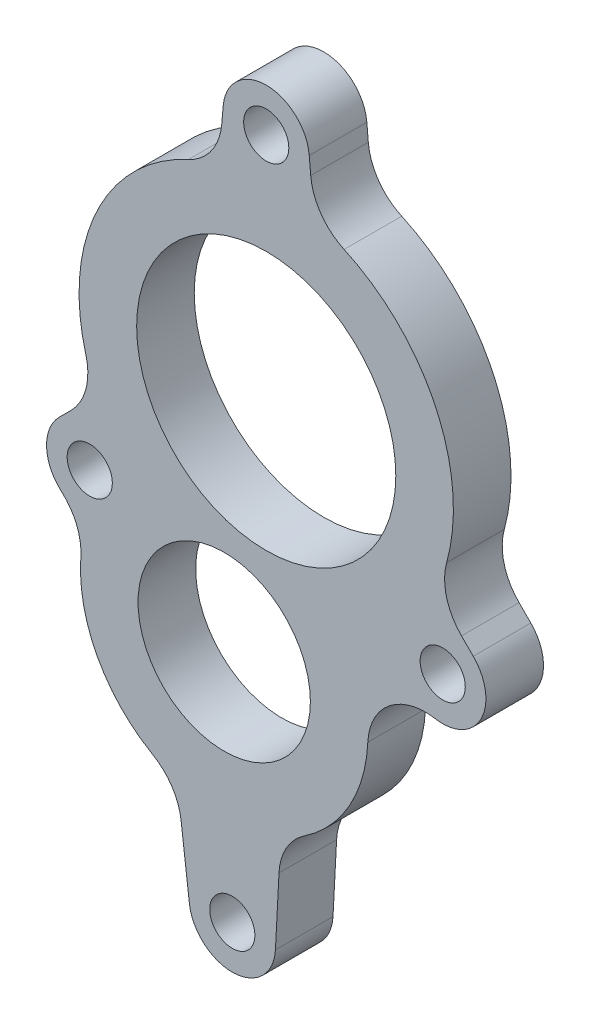
SolidWorks part; units mm, degrees
material "6061-T6 (SS)"
ref_plane "Front Plane" through (0, 0, 0) normal (0, 0, 1) x (1, 0, 0)
ref_plane "Top Plane" through (0, 0, 0) normal (0, 1, 0) x (1, 0, 0)
ref_plane "Right Plane" through (0, 0, 0) normal (1, 0, 0) x (0, 0, -1)
sketch "Sketch1" plane through (0, 0, 0) normal (0, 0, 1) x (1, 0, 0)
  line L0 (0, 0) -> (0, 25.4) construction
  line L1 (0, 0) -> (19.4575, -16.3268) construction
  line L2 (0, 0) -> (-19.4575, -16.3268) construction
  line L3 (-4.7444, 25.8151) -> (-5.2569, 19.9567)
  line L4 (4.7444, 25.8151) -> (5.2569, 19.9567)
  line L5 (22.8251, -12.9592) -> (18.6668, -8.8009)
  line L6 (16.7259, -20.228) -> (11.9087, -16.855)
  line L7 (-16.7259, -20.228) -> (-11.9087, -16.855)
  line L8 (-18.6668, -8.8009) -> (-22.8251, -12.9592)
  circle A0 centre (19.4575, -16.3268) radius 4.7625
  circle A1 centre (0, 25.4) radius 4.7625
  circle A2 centre (-19.4575, -16.3268) radius 4.7625
  circle A3 centre (19.4575, -16.3268) radius 2.4892
  circle A4 centre (-19.4575, -16.3268) radius 2.4892
  circle A5 centre (0, 25.4) radius 2.4892
  circle A6 centre (0, 0) radius 14.2875
  circle A7 centre (0, 0) radius 20.6375
  dimension "D1" = 9.525
  dimension "D4" = 4.9784
  dimension "D13" = 6.35
  dimension "D14" = 28.575
  dimension "D2" = 25.4
  dimension "D5" = 130
  dimension "D6" = 130
  dimension "D7" = 5
  dimension "D8" = 5
  dimension "D9" = 5
  dimension "D10" = 5
  dimension "D11" = 5
  dimension "D12" = 5
extrude "Boss-Extrude1" add sketch "Sketch1" along normal mid plane 6.35 contours A7 A6 | A7 L4 A1 L3 | A7 L6 A0 L5 | A7 L8 A2 L7 | A2 A4 | A1 A5 | A0 A3 | A7 A2 L7 | A7 L6 A0 | A7 A1 L3 region at (-3.9194, 21.5843, 0) region at (0, 30.0278, 0) region at (-2.5754, 19.8877, 0) region at (3.9194, 21.5843, 0) region at (-19.0539, -10.8717, 0) region at (-19.2557, -11.7034, 0) region at (-14.0152, -16.8766, 0) region at (19.0539, -10.8717, 0) region at (14.0152, -16.8766, 0) region at (23.7331, -14.5558, 0)
sketch "Sketch48" plane through (0, 0, 0) normal (0, 0, 1) x (1, 0, 0)
  line L0 (0, 0) -> (-4.6323, -26.2646) construction
  line L1 (1.0144, -51.8975) -> (1.592, -40.8409)
  line L2 (-8.4685, -52.2302) -> (-9.8196, -41.2413)
  line L3 (-4.6323, -26.2646) -> (-3.7416, -51.649) construction
  line L4 (16.7259, -20.228) -> (11.9087, -16.855) construction
  line L5 (16.7259, -20.228) -> (11.9087, -16.855)
  circle A0 centre (-4.6323, -26.2646) radius 9.4996
  circle A2 centre (-4.6323, -26.2646) radius 15.8496
  circle A3 centre (0, 25.4) radius 2.4892 construction
  circle A4 centre (-19.4575, -16.3268) radius 2.4892 construction
  circle A5 centre (0, 0) radius 14.2875 construction
  arc A6 (-11.9087, -16.855) -> (11.9087, -16.855) centre (0, 0) ccw construction
  circle A7 centre (-19.4575, -16.3268) radius 2.4892
  circle A8 centre (0, 0) radius 14.2875
  arc A9 (-11.9087, -16.855) -> (11.9087, -16.855) centre (0, 0) ccw
  circle A10 centre (-3.7416, -51.649) radius 4.7625
  circle A11 centre (-3.7416, -51.649) radius 2.4892
  arc A12 (-22.8251, -12.9592) -> (-16.7259, -20.228) centre (-19.4575, -16.3268) ccw construction
  circle A13 centre (19.4575, -16.3268) radius 2.4892 construction
  arc A14 (11.2009, -26.9848) -> (18.6376, -21.0182) centre (17.5444, -27.2734) cw
  circle A15 centre (19.4575, -16.3268) radius 4.7625 construction
  circle A16 centre (19.4575, -16.3268) radius 4.7625
  dimension "D3" = 18.9992
  dimension "D9" = 6.35
  dimension "D1" = 26.67
  dimension "D2" = 51.8719
  dimension "D5" = 77.1398
  dimension "D6" = 5
  dimension "D7" = 5
  dimension "D8" = 25.4
  dimension "D4" = 6.35
extrude "Boss-Extrude2" add sketch "Sketch48" along normal mid plane 6.35 contours L0 A8 A2 A7 A9 A0 | A10 L1 A2 L2 | A10 A11 | A16 L5 A9 A2 A14 region at (-3.9769, -44.9447, 0) region at (-3.5793, -56.274, 0) region at (-4.0921, -41.6609, 0) region at (12.6095, -20.4087, 0)
extrude "Cut-Extrude1" cut sketch "Sketch48<3>" against normal through all both and the other way through all contours L0 A0 A9 | A0 L0 A9 region at (-3.306, -18.7445, 0)
sketch "Sketch48<3>" plane through (0, 0, 0) normal (0, 0, 1) x (1, 0, 0) same geometry as "Sketch48"
fillet "Fillet1" radius 6.35 7 edges at (18.6668, -8.8009, 0) (-18.6668, -8.8009, 0) (-5.2569, 19.9567, 0) (5.2569, 19.9567, 0) (1.592, -40.8409, 0) (-19.6123, -21.0868, 0) (-9.8196, -41.2413, 0)
equation "\"D7@Sketch48\"=\"D6@Sketch48\""
